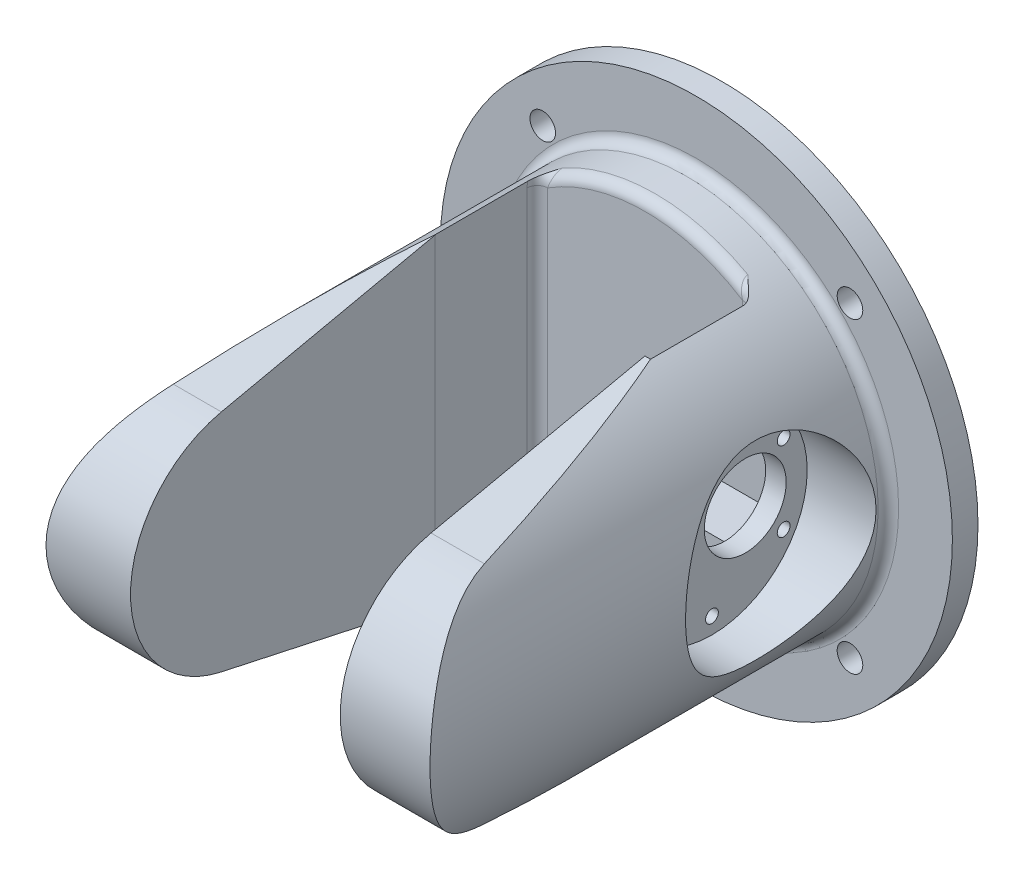
SolidWorks part; units mm, degrees
ref_plane "Alzado" through (0, 0, 0) normal (0, 0, 1) x (1, 0, 0)
ref_plane "Planta" through (0, 0, 0) normal (0, 1, 0) x (1, 0, 0)
ref_plane "Vista lateral" through (0, 0, 0) normal (1, 0, 0) x (0, 0, -1)
sketch "Croquis1" plane through (0, 0, 0) normal (0, 0, 1) x (1, 0, 0)
  circle A0 centre (0, 0) radius 50
  circle A1 centre (-30, 30) radius 2.5
  circle A2 centre (30, 30) radius 2.5
  circle A3 centre (30, -30) radius 2.5
  circle A4 centre (-30, -30) radius 2.5
  dimension "D1" = 100
  dimension "D2" = 5
  dimension "D5" = 30
  dimension "D6" = 30
  dimension "D3" = 2
  dimension "D4" = 2
extrude "Saliente-Extruir1" add sketch "Croquis1" along normal blind 5
sketch "Croquis2" plane through (0, 0, 5) normal (0, 0, 1) x (1, 0, 0)
  circle A0 centre (0, 0) radius 37.5
  dimension "D1" = 75
extrude "Saliente-Extruir2" add sketch "Croquis2" along normal blind 10
fillet "Redondeo1" radius 2 1 edges at (37.5, 0, 5)
sketch "Croquis3" plane through (0, 0, 15) normal (0, 0, 1) x (1, 0, 0)
  line L0 (-21.0461, 31.0373) -> (-21.0461, -31.0373)
  line L1 (0, 40.4736) -> (0, -41.2832) construction
  line L2 (21.0461, 31.0373) -> (21.0461, -31.0373)
  arc A0 (-21.0461, 31.0373) -> (-21.0461, -31.0373) centre (0, 0) ccw
  circle A1 centre (0, 0) radius 37.5 construction
  arc A2 (21.0461, 31.0373) -> (21.0461, -31.0373) centre (0, 0) cw
extrude "Saliente-Extruir4" add sketch "Croquis3" along normal blind 20
sketch "Croquis6" plane through (-21.0461, 0, 0) normal (1, 0, 0) x (0, 0, -1)
  line L0 (-76.7637, -21.9899) -> (-35, -31.0373)
  line L1 (-35, -31.0373) -> (-35, 31.0373)
  line L2 (-35, 31.0373) -> (-76.7637, 21.9899)
  line L3 (-7, 37.5) -> (-7, -37.5) construction
  line L11 (-35.2836, 28.9681) -> (-35.2836, -28.9681) construction
  arc A0 (-76.7637, 21.9899) -> (-76.7637, -21.9899) centre (-72, 0) ccw
  dimension "D1" = 45
  dimension "D2" = 65
  dimension "D3" = 0
fillet "Redondeo14" radius 2 2 edges at (0, 37.5, 15) (0, -37.5, 15)
extrude "Saliente-Extruir6" add sketch "Croquis6" along normal blind 60 and the other way blind 20
sketch "Croquis8" plane through (0, 0, 35) normal (0, 0, -1) x (-1, 0, 0)
  line L0 (21.0461, 31.0373) -> (41.0461, 31.0373)
  line L1 (41.0461, 31.0373) -> (41.0461, -31.0373)
  line L2 (41.0461, -31.0373) -> (21.0461, -31.0373)
  arc A0 (21.0461, -31.0373) -> (21.0461, 31.0373) centre (0, 0) ccw
  arc A1 (21.0461, -31.0373) -> (21.0461, 31.0373) centre (0, 0) ccw construction
  dimension "D1" = 0
extrude "Cortar-Extruir2" cut sketch "Croquis8" against normal blind 90
sketch "Croquis9" plane through (0, 0, 35) normal (0, 0, -1) x (-1, 0, 0)
  line L0 (-21.0461, 31.0373) -> (-38.9539, 31.0373)
  line L1 (-38.9539, 31.0373) -> (-38.9539, -31.0373)
  line L2 (-38.9539, -31.0373) -> (-21.0461, -31.0373)
  arc A0 (-21.0461, -31.0373) -> (-21.0461, 31.0373) centre (0, 0) cw
  arc A1 (-21.0461, 31.0373) -> (-21.0461, -31.0373) centre (0, 0) ccw construction
  dimension "D1" = 0
extrude "Cortar-Extruir3" cut sketch "Croquis9" against normal blind 90
sketch "Croquis10" plane through (0, 0, 15) normal (0, 0, 1) x (1, 0, 0)
  line L5 (-19.643, 28.9681) -> (19.643, 28.9681)
  line L6 (-19.643, 28.9681) -> (-19.643, -28.9681)
  line L7 (-19.643, -28.9681) -> (19.643, -28.9681)
  line L8 (19.643, 28.9681) -> (19.643, -28.9681)
extrude "Cortar-Extruir4" cut sketch "Croquis10" along normal blind 90
fillet "Redondeo10" radius 2 6 edges at (-21.0461, 0, 15) (21.0461, 0, 15) (-21.0461, -30.1967, 14.5136) (-21.0461, 30.3069, 14.4305) (21.0461, 30.1967, 14.5136) (21.0461, -30.3069, 14.4305)
sketch "Croquis13" plane through (21.0461, 0, 0) normal (-1, 0, 0) x (0, 0, 1)
  line L0 (5, -39.5) -> (5, 39.5) construction
  circle A0 centre (26, 0) radius 18.6
  dimension "D1" = 37.2
  dimension "D2" = 21
extrude "Cortar-Extruir8" cut sketch "Croquis13" against normal blind 18.05
sketch "Croquis19" plane through (0, 0, 15) normal (0, 0, 1) x (1, 0, 0)
  line L0 (21.0461, 29.9583) -> (21.0461, 16.2776) construction
  line L1 (21.0461, 12.368) -> (4.0461, 12.368)
  line L2 (21.0461, 12.368) -> (21.0461, -12.632)
  line L3 (21.0461, -12.632) -> (4.0461, -12.632)
  line L4 (4.0461, 12.368) -> (4.0461, -12.632)
  dimension "D1" = 25
  dimension "D2" = 17
extrude "Cortar-Extruir11" cut sketch "Croquis19" against normal blind 10 and the other way blind 10
sketch "Croquis15" plane through (21.0461, 0, 0) normal (-1, 0, 0) x (0, 0, 1)
  circle A0 centre (26, 0) radius 19
  arc A1 (35, 16.2776) -> (17, 16.2776) centre (26, 0) ccw construction
  circle A2 centre (19.5, 0) radius 8
  circle A3 centre (40, -7.75) radius 1.25
  circle A4 centre (40, 7.75) radius 1.25
  circle A5 centre (26, -15.4) radius 1.25
  circle A6 centre (26, 15.4) radius 1.25
  circle A7 centre (12, 7.75) radius 1.25
  circle A8 centre (12, -7.75) radius 1.25
  dimension "D1" = 38
  dimension "D3" = 16
  dimension "D5" = 2.5
  dimension "D6" = 2.5
  dimension "D7" = 15.5
  dimension "D8" = 20.5
  dimension "D9" = 7.75
  dimension "D10" = 2.5
  dimension "D11" = 2.5
  dimension "D12" = 30.8
  dimension "D13" = 14
  dimension "D14" = 7.65
  dimension "D15" = 2
  dimension "D2" = 0
  dimension "D4" = 6.5
extrude "Saliente-Extruir7" add sketch "Croquis15" against normal blind 3 and the other way blind 1
sketch "Croquis20" plane through (0, 36.8882, 7.9912) normal (0, 0.9773, 0.2117) x (1, 0, 0)
  line L0 (19.643, -37.4083) -> (19.643, -70.3678) construction
  line L1 (-19.643, -37.4083) -> (19.643, -37.4083)
  line L2 (-19.643, -37.4083) -> (-19.643, -26.8508)
  line L3 (-19.643, -26.8508) -> (19.643, -26.8508)
  line L4 (19.643, -37.4083) -> (19.643, -26.8508)
  dimension "D1" = 0
extrude "Cortar-Extruir12" cut sketch "Croquis20" against normal blind 10
sketch "Croquis21" plane through (0, -36.8882, 7.9912) normal (0, -0.9773, 0.2117) x (-1, 0, 0)
  line L0 (-19.643, -70.3678) -> (-19.643, -37.4083) construction
  line L1 (19.643, -37.4083) -> (-19.643, -37.4083)
  line L2 (19.643, -37.4083) -> (19.643, -26.9293)
  line L3 (19.643, -26.9293) -> (-19.643, -26.9293)
  line L4 (-19.643, -37.4083) -> (-19.643, -26.9293)
  dimension "D1" = 0
extrude "Cortar-Extruir13" cut sketch "Croquis21" against normal blind 70
sketch "Croquis22" plane through (-19.643, 0, 0) normal (1, 0, 0) x (0, 0, -1)
  line L1 (-33.7961, 31.8464) -> (-106.8703, 31.8464)
  line L2 (-33.7961, 31.8464) -> (-33.7961, -39.5911)
  line L3 (-33.7961, -39.5911) -> (-106.8703, -39.5911)
  line L4 (-106.8703, 31.8464) -> (-106.8703, -39.5911)
extrude "Cortar-Extruir14" cut sketch "Croquis22" against normal blind 1.35 and the other way blind 39.6
